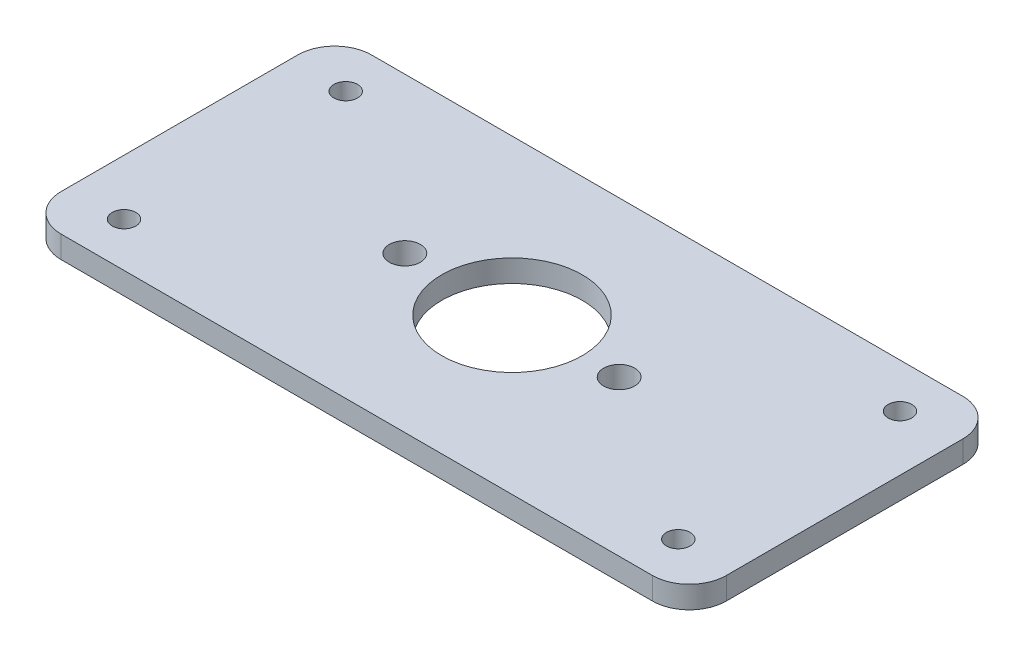
SolidWorks part; units mm, degrees
material "Carbon Fiber"
ref_plane "Front Plane" through (0, 0, 0) normal (0, 0, 1) x (1, 0, 0)
ref_plane "Top Plane" through (0, 0, 0) normal (0, 1, 0) x (1, 0, 0)
ref_plane "Right Plane" through (0, 0, 0) normal (1, 0, 0) x (0, 0, -1)
sketch "Sketch1" plane through (0, 0, 0) normal (0, 1, 0) x (1, 0, 0)
  line L0 (0, 21) -> (90, 21) construction
  line L1 (0, 0) -> (90, 0)
  line L2 (0, 0) -> (0, 42)
  line L3 (0, 42) -> (90, 42)
  line L4 (90, 0) -> (90, 42)
  line L5 (45, 42) -> (45, 0) construction
  line L6 (7.5, 42) -> (7.5, 0) construction
  circle A0 centre (45, 21) radius 9.5
  circle A1 centre (59.5, 21) radius 2.1
  circle A2 centre (30.5, 21) radius 2.1
  circle A3 centre (7.5, 36) radius 1.6
  circle A4 centre (7.5, 6) radius 1.6
  circle A5 centre (82.5, 6) radius 1.6
  circle A6 centre (82.5, 36) radius 1.6
  dimension "D3" = 19
  dimension "D4" = 4.2
  dimension "D5" = 29
  dimension "D6" = 3.2
  dimension "D7" = 30
  dimension "D1" = 90
  dimension "D2" = 42
  dimension "D8" = 7.5
extrude "Boss-Extrude1" add sketch "Sketch1" along normal blind 3
fillet "Fillet1" radius 5 4 edges at (90, 1.5, -42) (90, 1.5, 0) (0, 1.5, 0) (0, 1.5, -42)
